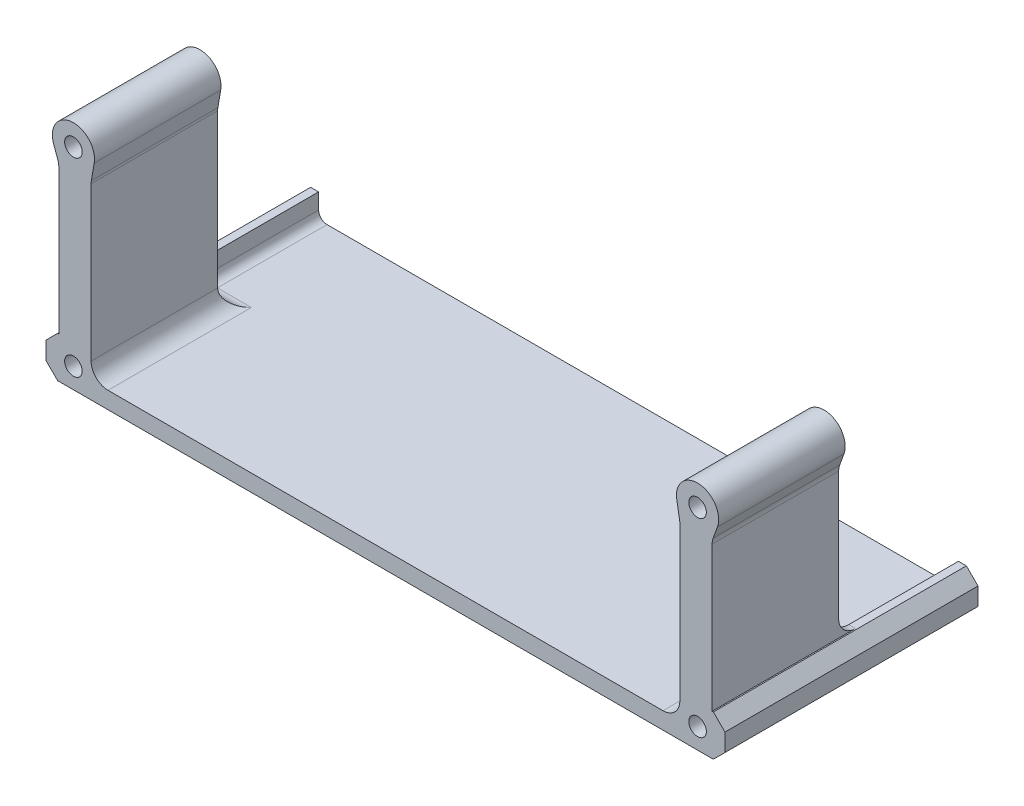
SolidWorks part; units mm, degrees
ref_plane "Plane XZ" through (0, 0, 0) normal (0, 0, 1) x (1, 0, 0)
ref_plane "Plane XY" through (0, 0, 0) normal (0, 1, 0) x (1, 0, 0)
ref_plane "Plane YZ" through (0, 0, 0) normal (1, 0, 0) x (0, 0, -1)
sketch "Sketch1" plane through (0, 0, 0) normal (0, 0, 1) x (1, 0, 0)
  line L0 (0, 0) -> (-49.53, 0) construction
  line L1 (0, 0) -> (0, 13.019) construction
  line L2 (-49.53, 3.175) -> (-49.53, -3.175) construction
  line L3 (-49.53, 3.175) -> (-51.435, 1.27) construction
  line L4 (-51.435, 1.27) -> (-51.435, -1.27) construction
  line L5 (-51.435, -1.27) -> (-49.53, -3.175) construction
  line L6 (-51.435, 0) -> (-49.53, 0) construction
  line L7 (-49.4402, 3.0852) -> (-51.308, 1.2174)
  line L8 (-51.308, 1.2174) -> (-51.308, -1.2174)
  line L9 (-51.308, -1.2174) -> (-49.4402, -3.0852)
  line L10 (-49.4402, 3.0852) -> (-48.1702, 3.0852)
  line L11 (-48.1702, 3.0852) -> (-48.1702, -0.5452)
  line L12 (-48.1702, -0.5452) -> (48.1702, -0.5452)
  line L13 (-49.4402, -3.0852) -> (49.4402, -3.0852)
  line L14 (51.308, -1.2174) -> (49.4402, -3.0852)
  line L15 (51.308, 1.2174) -> (51.308, -1.2174)
  line L16 (49.4402, 3.0852) -> (51.308, 1.2174)
  line L17 (49.4402, 3.0852) -> (48.1702, 3.0852)
  line L18 (48.1702, 3.0852) -> (48.1702, -0.5452)
  point P20 (0, -3.0852)
  point P25 (0, -0.5452)
  dimension "D1" = 51.435
  dimension "D2" = 2.54
  dimension "D3" = 1.905
  dimension "D4" = 45
  dimension "D6" = 1.27
  dimension "D7" = 2.54
  dimension "D5" = 0.127
extrude "Boss-Extrude1" add sketch "Sketch1" against normal blind 101.6
ref_plane "Plane2" through (0, 14.2875, 0) normal (0, 1, 0) x (1, 0, 0)
sketch "Sketch3" plane through (0, 0, -101.6) normal (0, 0, -1) x (-1, 0, 0)
  line L1 (48.1702, -0.5452) -> (29.1202, -0.5452)
  line L2 (48.1702, -0.5452) -> (48.1702, 14.6948)
  line L3 (48.1702, 14.6948) -> (29.1202, 14.6948)
  line L4 (29.1202, -0.5452) -> (29.1202, 14.6948)
  dimension "D1" = 19.05
  dimension "D2" = 15.24
extrude "Boss-Extrude3" add sketch "Sketch3" against normal blind 2.54
ref_plane "Plane1" through (-38.6452, 0, 0) normal (1, 0, 0) x (0, 0, -1)
sketch "Sketch4" plane through (-29.1202, 0, 0) normal (1, 0, 0) x (0, 0, -1)
  line L0 (99.06, 14.6948) -> (83.82, -0.5452)
  line L1 (83.82, -0.5452) -> (99.06, -0.5452)
  line L2 (99.06, -0.5452) -> (99.06, 14.6948)
extrude "Boss-Extrude4" add sketch "Sketch4" against normal blind 3.175
mirror "Mirror1" about plane through (-38.6452, 0, 0) normal (1, 0, 0) of "Boss-Extrude4"
sketch "Sketch5" plane through (0, 0, -99.06) normal (0, 0, 1) x (1, 0, 0)
  line L0 (-44.9952, 6.985) -> (-32.2952, 6.985) construction
  line L3 (50, 0) -> (-50, 0) construction
  line L4 (-44.9952, -0.5452) -> (-44.9952, 14.6948) construction
  line L5 (-32.2952, -0.5452) -> (-32.2952, 14.6948) construction
  line L6 (0, 0) -> (0, 12.2749) construction
  circle A0 centre (-38.6334, 6.985) radius 3.9687
  dimension "D1" = 7.9375
  dimension "D2" = 6.985
  dimension "D3" = 38.6334
extrude "Cut-Extrude1" cut sketch "Sketch5" against normal through all
sketch "Sketch6" plane through (0, 0, 0) normal (0, 0, 1) x (1, 0, 0)
  line L0 (0, 28.575) -> (0, 0) construction
  line L1 (-46.99, 28.575) -> (46.99, 28.575) construction
  line L2 (-46.99, 28.575) -> (-46.99, 0) construction
  line L3 (-46.99, 0) -> (46.99, 0) construction
  line L4 (46.99, 28.575) -> (46.99, 0) construction
  line L5 (0, -50) -> (0, 50) construction
  line L6 (0, 14.2875) -> (46.99, 14.2875) construction
  line L7 (50, 0) -> (-50, 0) construction
  circle A0 centre (46.99, 0) radius 1.3208
  circle A1 centre (-46.99, 0) radius 1.3208
  circle A2 centre (46.99, 28.575) radius 1.3208
  circle A3 centre (-46.99, 28.575) radius 1.3208
  dimension "D5" = 2.6416
  dimension "D1" = 28.575
  dimension "D2" = 93.98
  dimension "D3" = 14.2875
sketch "Sketch18" plane through (0, 3.0852, 0) normal (0, 1, 0) x (1, 0, 0)
  line L0 (0, 0) -> (0, 16.9563) construction
  line L1 (48.1702, 0) -> (44.323, 0)
  line L2 (48.1702, 0) -> (48.1702, 19.05)
  line L3 (48.1702, 19.05) -> (44.323, 19.05)
  line L4 (44.323, 0) -> (44.323, 19.05)
  line L5 (-48.1702, 0) -> (-44.323, 0)
  line L6 (-48.1702, 0) -> (-48.1702, 19.05)
  line L7 (-48.1702, 19.05) -> (-44.323, 19.05)
  line L8 (-44.323, 0) -> (-44.323, 19.05)
  dimension "D1" = 88.646
  dimension "D2" = 19.05
extrude "Boss-Extrude9" add sketch "Sketch18" against normal up to surface (3.6304 mm away) up to face at (-21.2821, -0.5452, -73.66)
sketch "Sketch39" plane through (0, 0, 0) normal (0, 0, 1) x (1, 0, 0)
  line L0 (49.4402, 3.0852) -> (44.323, 3.0852) construction
  line L1 (49.1862, 3.0852) -> (44.323, 3.0852)
  line L2 (49.1862, 3.0852) -> (49.1862, 25.3259)
  line L3 (49.1862, 25.3259) -> (44.323, 25.3259) construction
  line L4 (44.323, 3.0852) -> (44.323, 25.3259)
  line L5 (44.323, -0.5452) -> (44.323, 3.0852) construction
  line L6 (49.1862, 25.3259) -> (49.9735, 27.4891)
  line L7 (44.323, 25.3259) -> (43.8601, 28.0415)
  circle A1 centre (46.99, 28.575) radius 3.175 construction
  arc A2 (43.8601, 28.0415) -> (49.9735, 27.4891) centre (46.99, 28.575) cw
  dimension "D1" = 0.254
  dimension "D2" = 6.35
  dimension "D3" = 20
extrude "Boss-Extrude17" add sketch "Sketch39" against normal up to surface (19.05 mm away) up to face at (46.2466, 1.27, -19.05)
mirror "Mirror5" about plane through (0, 0, 0) normal (1, 0, 0) of "Boss-Extrude17"
sketch "Sketch20" plane through (0, 0, 0) normal (0, 0, 1) x (1, 0, 0)
  circle A0 centre (46.99, 0) radius 1.3208 construction
  circle A1 centre (46.99, 0) radius 1.3208
  circle A2 centre (-46.99, 0) radius 1.3208 construction
  circle A3 centre (-46.99, 0) radius 1.3208
  circle A4 centre (-46.99, 28.575) radius 1.3208 construction
  circle A5 centre (-46.99, 28.575) radius 1.3208
  circle A6 centre (46.99, 28.575) radius 1.3208 construction
  circle A7 centre (46.99, 28.575) radius 1.3208
extrude "Cut-Extrude7" cut sketch "Sketch20" against normal blind 7.62
fillet "Fillet3" radius 2.54 4 edges at (-49.1862, 25.3259, -9.525) (-44.323, 25.3259, -9.525) (49.1862, 25.3259, -9.525) (44.323, 25.3259, -9.525)
fillet "Fillet4" radius 2.54 6 edges at (46.2466, -0.5452, -19.05) (-46.2466, -0.5452, -19.05) (44.323, -0.5452, -9.525) (-44.323, -0.5452, -9.525) (-48.6782, 3.0852, -19.05) (48.6782, 3.0852, -19.05)
sketch "Sketch40" plane through (0, 0, 0) normal (0, 0, 1) x (1, 0, 0)
  line L5 (-49.1862, 3.0852) -> (-49.4402, 3.0852) construction
  line L14 (-49.3684, 3.0852) -> (-51.1175, 1.3361)
  line L15 (-51.1175, 1.3361) -> (-51.1175, -1.3361)
  line L16 (-51.1175, -1.3361) -> (-49.3684, -3.0852)
  line L17 (-49.4402, -3.0852) -> (49.4402, -3.0852) construction
  line L18 (-51.308, -1.2174) -> (-49.4402, -3.0852) construction
  line L19 (-51.308, 1.2174) -> (-51.308, -1.2174) construction
  line L20 (-49.4402, 3.0852) -> (-51.308, 1.2174) construction
  line L21 (-49.3684, 3.0852) -> (-52.3875, 3.0852)
  line L22 (-52.3875, 3.0852) -> (-52.3875, -3.0852)
  line L23 (-52.3875, -3.0852) -> (-49.3684, -3.0852)
  line L24 (0, -17.7849) -> (0, 18.9879) construction
  line L25 (52.3875, 3.0852) -> (52.3875, -3.0852)
  line L26 (49.3684, 3.0852) -> (52.3875, 3.0852)
  line L27 (49.3684, 3.0852) -> (51.1175, 1.3361)
  line L28 (51.1175, 1.3361) -> (51.1175, -1.3361)
  line L29 (51.1175, -1.3361) -> (49.3684, -3.0852)
  line L30 (52.3875, -3.0852) -> (49.3684, -3.0852)
  dimension "D1" = 0.0508
  dimension "D2" = 0.1905
  dimension "D3" = 1.27
extrude "Cut-Extrude19" cut sketch "Sketch40" against normal through all
fillet "Fillet12" radius 0.508 1 edges at (-48.1702, 3.0852, -94.5252)
fillet "Fillet24" radius 1.27 3 edges at (-48.1702, -0.5452, -52.705) (-48.1702, 3.81, -19.05) (-48.1702, 0.1988, -19.7939)
sketch "Sketch41" plane through (0, -0.5452, 0) normal (0, 1, 0) x (1, 0, 0)
  line L0 (41.783, 0) -> (-41.783, 0) construction
  line L1 (81.5824, 124.5944) -> (-78.3751, 124.5944)
  line L2 (81.5824, 124.5944) -> (81.5824, 38.1)
  line L3 (81.5824, 38.1) -> (-78.3751, 38.1)
  line L4 (-78.3751, 124.5944) -> (-78.3751, 38.1)
  dimension "D1" = 38.1
extrude "Cut-Extrude20" cut sketch "Sketch41" against normal through all both and the other way through all
